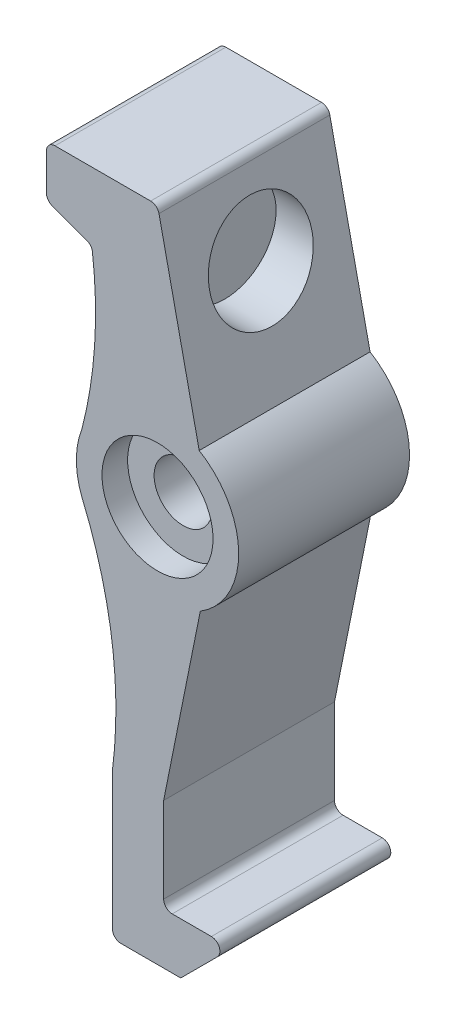
SolidWorks part; units mm, degrees
ref_plane "Спереди" through (0, 0, 0) normal (0, 0, 1) x (1, 0, 0)
ref_plane "Сверху" through (0, 0, 0) normal (0, 1, 0) x (1, 0, 0)
ref_plane "Справа" through (0, 0, 0) normal (1, 0, 0) x (0, 0, -1)
sketch "Эскиз1" plane through (0, 0, 0) normal (0, 0, 1) x (1, 0, 0)
  line L6 (-1000, 0) -> (49000, 0) construction
  line L7 (0, -1000) -> (0, 49000) construction
  line L16 (-6, 15.3) -> (-0.403, 15.3)
  line L17 (0.0856, 14.9062) -> (2.44, 4.0754)
  line L18 (0.3592, -14.7) -> (2.5033, -4.0368)
  line L19 (0.3592, -14.7) -> (0.3592, -19.7)
  line L20 (0.8592, -20.2) -> (3.1521, -20.2)
  line L21 (3.5056, -21.0536) -> (1.3592, -23.2)
  line L22 (1.3592, -23.2) -> (-2.1408, -23.2)
  line L23 (-2.6408, -22.7) -> (-2.6408, -14.7)
  line L24 (-6.5, 14.8) -> (-6.5, 12.6501)
  line L25 (-6.171, 12.1803) -> (-4.136, 11.4396)
  circle A12 centre (0, 0) radius 4.75
  circle A15 centre (0, 0) radius 3.25
  circle A16 centre (0, 0) radius 1.7
  arc A17 (-4.4287, -1.7173) -> (-2.6408, -14.7) centre (-27.4352, -11.5) cw
  arc A18 (-4.4287, 1.7173) -> (-3.8107, 11.0303) centre (-28.6264, 8) ccw
  arc A19 (-4.136, 11.4396) -> (-3.8107, 11.0303) centre (-4.307, 10.9697) cw
  arc A20 (-0.403, 15.3) -> (0.0856, 14.9062) centre (-0.403, 14.8) cw
  arc A21 (-6.5, 12.6501) -> (-6.171, 12.1803) centre (-6, 12.6501) ccw
  arc A22 (-6, 15.3) -> (-6.5, 14.8) centre (-6, 14.8) ccw
  arc A23 (0.3592, -19.7) -> (0.8592, -20.2) centre (0.8592, -19.7) ccw
  arc A24 (3.1521, -20.2) -> (3.5056, -21.0536) centre (3.1521, -20.7) cw
  arc A25 (-2.1408, -23.2) -> (-2.6408, -22.7) centre (-2.1408, -22.7) cw
  point P81 (0, 15.3)
  point P84 (-6.5, 12.3)
  point P87 (4.75, 0)
  point P88 (-6.5, 15.3)
  point P91 (0.3592, -20.2)
  point P94 (4.3592, -20.2)
  point P97 (-2.6408, -23.2)
  dimension "D3" = 8
  dimension "D4" = 9.5
  dimension "D14" = 6.5
  dimension "D15" = 3.4
  dimension "D22" = 3
  dimension "D23" = 25
  dimension "D24" = 6.5
  dimension "D29" = 0.5
  dimension "D16" = 3
  dimension "D17" = 45
  dimension "D18" = 7
  dimension "D19" = 3
  dimension "D20" = 38.5
  dimension "D21" = 20
  dimension "D25" = 20.2
  dimension "D26" = 19.5
  dimension "D27" = 5.5
  dimension "D28" = 1.1912
extrude "Бобышка-Вытянуть1" add sketch "Эскиз1" along normal mid plane 10 contours L16 A22 L24 A21 L25 A19 A18 A12 L17 A20 | A12 A17 A15 | A15 A16 | A25 L22 L21 A24 L20 A23 L19 L18 A12 A17 L23 region at (-1.8656, 9.9305, 0) region at (4.0155, 2.276, 0) region at (-0.6157, -13.4897, 0) region at (-3.1581, 0, 0)
extrude "Вырез-Вытянуть1" cut sketch "Эскиз1<4>" against normal blind 1.5 from surface contours A15 A16 region at (-3.1581, 0, 0) starting at face at (-1.5185, -3.4193, 5)
sketch "Эскиз1<4>" plane through (0, 0, 0) normal (0, 0, 1) x (1, 0, 0) same geometry as "Эскиз1"
extrude "Вырез-Вытянуть2" cut sketch "Эскиз1<5>" along normal blind 1.5 from surface contours A15 A16 region at (-3.1581, 0, 0) starting at face at (-1.5185, -3.4193, -5)
sketch "Эскиз1<5>" plane through (0, 0, 0) normal (0, 0, 1) x (1, 0, 0) same geometry as "Эскиз1"
sketch "Эскиз2" plane through (0, 0.6819, 0) normal (1, 0, 0) x (0, 0, -1)
  line L0 (0, -0.6819) -> (0, 9.8181) construction
  circle A0 centre (0, 9.8181) radius 3
  dimension "D2" = 6
  dimension "D1" = 10.5
extrude "Вырез-Вытянуть3" cut sketch "Эскиз2" against normal blind 3.5 from vertex starting at point (2.44, 4.0754, 5)
